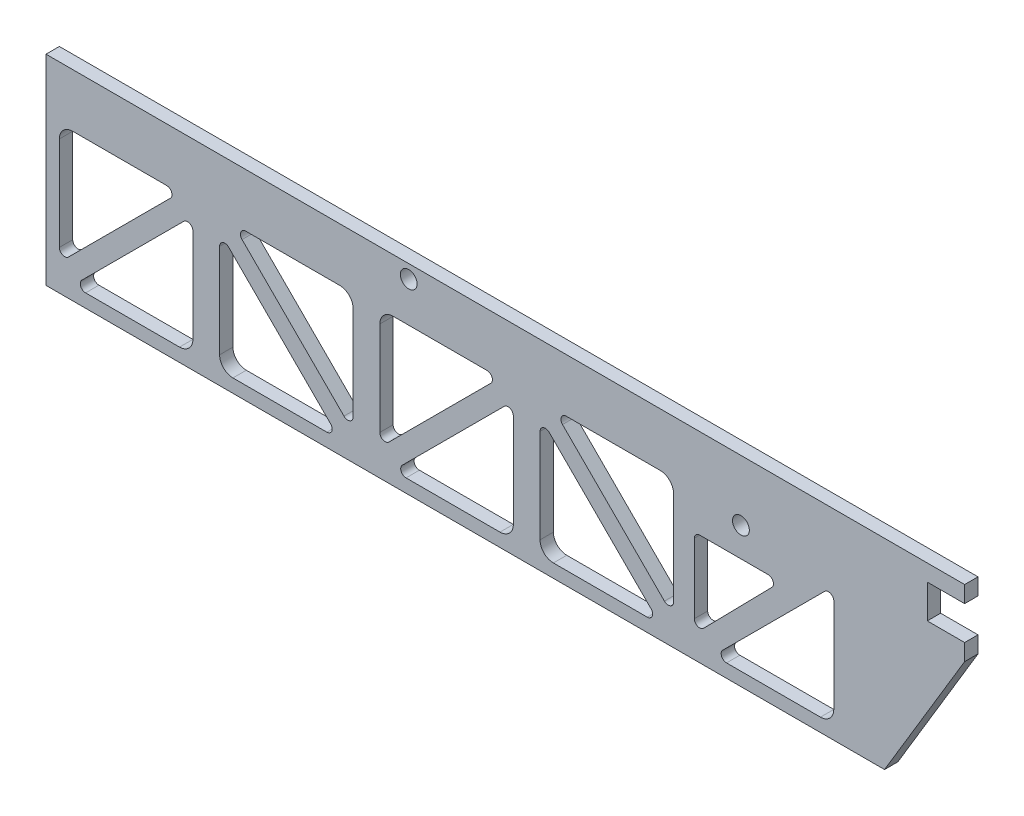
SolidWorks part; units mm, degrees
material "Pine"
ref_plane "Front Plane" through (0, 0, 0) normal (0, 0, 1) x (1, 0, 0)
ref_plane "Top Plane" through (0, 0, 0) normal (0, 1, 0) x (1, 0, 0)
ref_plane "Right Plane" through (0, 0, 0) normal (1, 0, 0) x (0, 0, -1)
sketch "Model" plane through (0, 0, 0) normal (0, 0, 1) x (1, 0, 0)
  line L0 (312.6855, 15.1239) -> (345.2281, 48.2988)
  line L1 (343.4149, 52.6175) -> (310.8722, 52.6175)
  line L2 (308.3322, 50.0775) -> (308.3322, 16.9026)
  line L8 (171.2321, 6.35) -> (215.9, 6.35)
  line L9 (217.9139, 59.1639) -> (169.4361, 10.6861)
  line L10 (222.25, 57.3679) -> (222.25, 12.7)
  line L11 (234.95, 57.3679) -> (234.95, 12.7)
  line L12 (239.2861, 59.1639) -> (287.7639, 10.6861)
  line L13 (241.3, 6.35) -> (285.9679, 6.35)
  line L14 (294.1139, 17.0361) -> (245.6361, 65.5139)
  line L15 (247.4321, 69.85) -> (292.1, 69.85)
  line L16 (298.45, 63.5) -> (298.45, 18.8321)
  line L17 (323.6321, 6.35) -> (368.3, 6.35)
  line L18 (370.3139, 59.1639) -> (321.8361, 10.6861)
  line L19 (374.65, 57.3679) -> (374.65, 12.7)
  line L20 (18.8321, 6.35) -> (63.5, 6.35)
  line L21 (17.0361, 10.6861) -> (65.5139, 59.1639)
  line L22 (69.85, 57.3679) -> (69.85, 12.7)
  line L23 (82.55, 57.3679) -> (82.55, 12.7)
  line L24 (86.8861, 59.1639) -> (135.3639, 10.6861)
  line L25 (88.9, 6.35) -> (133.5679, 6.35)
  line L26 (93.2361, 65.5139) -> (141.7139, 17.0361)
  line L27 (95.0321, 69.85) -> (139.7, 69.85)
  line L28 (146.05, 63.5) -> (146.05, 18.8321)
  line L29 (163.0861, 17.0361) -> (211.5639, 65.5139)
  line L30 (158.75, 63.5) -> (158.75, 18.8321)
  line L31 (165.1, 69.85) -> (209.7679, 69.85)
  line L35 (419.1, 87.376) -> (419.1, 71.374)
  line L36 (436.88, 87.376) -> (419.1, 87.376)
  line L37 (436.88, 87.376) -> (436.88, 95.25)
  line L38 (0, 95.25) -> (436.88, 95.25)
  line L39 (0, 0) -> (0, 95.25)
  line L40 (0, 0) -> (398.78, 0)
  line L41 (436.88, 63.5) -> (398.78, 0)
  line L42 (436.88, 63.5) -> (436.88, 71.374)
  line L43 (419.1, 71.374) -> (436.88, 71.374)
  line L44 (6.35, 63.5) -> (6.35, 18.8321)
  line L45 (12.7, 69.85) -> (57.3679, 69.85)
  line L46 (59.1639, 65.5139) -> (10.6861, 17.0361)
  arc A0 (215.9, 6.35) -> (222.25, 12.7) centre (215.9, 12.7) ccw
  arc A1 (169.4361, 10.6861) -> (171.2321, 6.35) centre (171.2321, 8.89) ccw
  arc A2 (222.25, 57.3679) -> (217.9139, 59.1639) centre (219.71, 57.3679) ccw
  arc A3 (239.2861, 59.1639) -> (234.95, 57.3679) centre (237.49, 57.3679) ccw
  arc A4 (285.9679, 6.35) -> (287.7639, 10.6861) centre (285.9679, 8.89) ccw
  arc A5 (234.95, 12.7) -> (241.3, 6.35) centre (241.3, 12.7) ccw
  arc A6 (247.4321, 69.85) -> (245.6361, 65.5139) centre (247.4321, 67.31) ccw
  arc A7 (298.45, 63.5) -> (292.1, 69.85) centre (292.1, 63.5) ccw
  arc A8 (294.1139, 17.0361) -> (298.45, 18.8321) centre (295.91, 18.8321) ccw
  arc A9 (321.8361, 10.6861) -> (323.6321, 6.35) centre (323.6321, 8.89) ccw
  arc A10 (374.65, 57.3679) -> (370.3139, 59.1639) centre (372.11, 57.3679) ccw
  arc A11 (368.3, 6.35) -> (374.65, 12.7) centre (368.3, 12.7) ccw
  arc A12 (63.5, 6.35) -> (69.85, 12.7) centre (63.5, 12.7) ccw
  arc A13 (17.0361, 10.6861) -> (18.8321, 6.35) centre (18.8321, 8.89) ccw
  arc A14 (69.85, 57.3679) -> (65.5139, 59.1639) centre (67.31, 57.3679) ccw
  arc A15 (86.8861, 59.1639) -> (82.55, 57.3679) centre (85.09, 57.3679) ccw
  arc A16 (133.5679, 6.35) -> (135.3639, 10.6861) centre (133.5679, 8.89) ccw
  arc A17 (82.55, 12.7) -> (88.9, 6.35) centre (88.9, 12.7) ccw
  arc A18 (95.0321, 69.85) -> (93.2361, 65.5139) centre (95.0321, 67.31) ccw
  arc A19 (146.05, 63.5) -> (139.7, 69.85) centre (139.7, 63.5) ccw
  arc A20 (141.7139, 17.0361) -> (146.05, 18.8321) centre (143.51, 18.8321) ccw
  arc A21 (158.75, 18.8321) -> (163.0861, 17.0361) centre (161.29, 18.8321) ccw
  arc A22 (165.1, 69.85) -> (158.75, 63.5) centre (165.1, 63.5) ccw
  arc A23 (211.5639, 65.5139) -> (209.7679, 69.85) centre (209.7679, 67.31) ccw
  arc A24 (345.2281, 48.2988) -> (343.4149, 52.6175) centre (343.4149, 50.0775) ccw
  arc A25 (310.8722, 52.6175) -> (308.3322, 50.0775) centre (310.8722, 50.0775) ccw
  arc A26 (312.6855, 15.1239) -> (308.3322, 16.9026) centre (310.8722, 16.9026) cw
  arc A27 (6.35, 18.8321) -> (10.6861, 17.0361) centre (8.89, 18.8321) ccw
  arc A28 (12.7, 69.85) -> (6.35, 63.5) centre (12.7, 63.5) ccw
  arc A29 (59.1639, 65.5139) -> (57.3679, 69.85) centre (57.3679, 67.31) ccw
  circle A30 centre (172.4917, 88.8013) radius 4
  circle A31 centre (330.4797, 66.4493) radius 4
  point P75 (308.3322, 10.6861)
  dimension "D2" = 6.4487
  dimension "D3" = 172.4917
  dimension "D4" = 8
  dimension "D5" = 22.352
  dimension "D6" = 8
  dimension "D8" = 2.54
  dimension "D1" = 95.25
  dimension "D7" = 157.988
extrude "Boss-Extrude2" add sketch "Model" along normal blind 6.35
